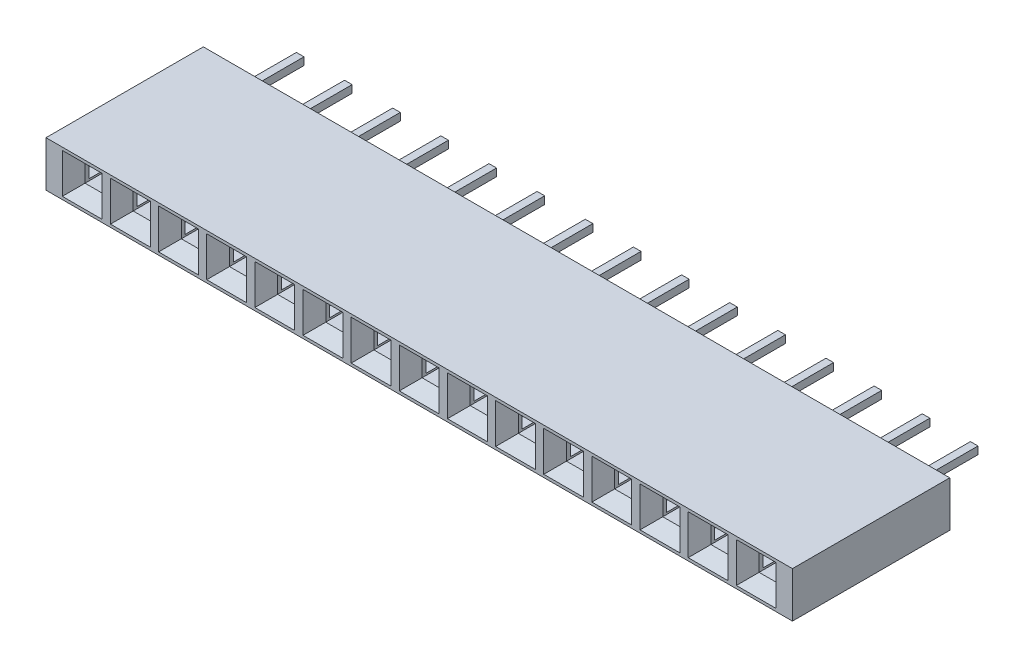
SolidWorks part; units mm, degrees
note: The reader was unsure of these and kept them because the rebuilt part matched: shared geometry of "Эскиз-БоковаяНакладка<2>".
other "Пластик"
ref_plane "Front Plane" through (0, 0, 0) normal (0, 0, 1) x (1, 0, 0)
ref_plane "Top Plane" through (0, 0, 0) normal (0, 1, 0) x (1, 0, 0)
ref_plane "Right Plane" through (0, 0, 0) normal (1, 0, 0) x (0, 0, -1)
sketch "Эскиз-ВнутреннееСечение" plane through (0, 0, 0) normal (0, 0, 1) x (1, 0, 0)
  line L0 (-1, 0.35) -> (-0.45, 0.35)
  line L1 (-1.27, -1.2) -> (1.27, -1.2)
  line L2 (-1.27, -1.2) -> (-1.27, 1.2)
  line L3 (-1.27, 1.2) -> (1.27, 1.2)
  line L4 (1.27, -1.2) -> (1.27, 1.2)
  line L5 (-1.27, -1.2) -> (1.27, 1.2) construction
  line L6 (-1.27, 1.2) -> (1.27, -1.2) construction
  line L8 (-1, -0.35) -> (-1, 0.35)
  line L9 (-0.45, 0.45) -> (0.45, 0.45)
  line L11 (0, 1.2) -> (0, -1.2) construction
  line L12 (0.45, 0.35) -> (0.45, 0.45)
  line L13 (-1.27, 0) -> (1.27, 0) construction
  line L14 (1, 0.35) -> (0.45, 0.35)
  line L15 (-0.45, 0.35) -> (-0.45, 0.45)
  line L16 (1, -0.35) -> (0.45, -0.35)
  line L17 (0.45, -0.35) -> (0.45, -0.45)
  line L18 (-0.45, -0.35) -> (-0.45, -0.45)
  line L19 (-1, -0.35) -> (-0.45, -0.35)
  line L20 (-0.45, -0.45) -> (0.45, -0.45)
  line L21 (1, -0.35) -> (1, 0.35)
  point P0 (0, 0)
  point P5 (0, 0)
  dimension "D1" = 2.4
  dimension "D2" = 2.54
  dimension "D3" = 1
  dimension "D4" = 0.35
  dimension "D5" = 0.1
  dimension "D7" = 0.55
extrude "Бобышка-ОтЦентраВверхВниз" add sketch "Эскиз-ВнутреннееСечение" against normal blind 0.4 and the other way blind 6.7 contours L8 L0 L15 L9 L12 L14 L21 L16 L17 L20 L18 L19
sketch "Эскиз-СамыйНиз" plane through (0, 0, -0.4) normal (0, 0, -1) x (-1, 0, 0)
  line L1 (1.27, 1.2) -> (1.27, -1.2) construction
  line L2 (-1.27, -1.2) -> (-1.27, 1.2) construction
  line L3 (0.45, -0.45) -> (-0.45, -0.45) construction
  line L4 (1.27, -1.2) -> (-1.27, -1.2)
  line L5 (1.27, -1.2) -> (1.27, -0.45)
  line L6 (1.27, -0.45) -> (-1.27, -0.45)
  line L7 (-1.27, -1.2) -> (-1.27, -0.45)
  line L9 (-1.27, 1.2) -> (1.27, 1.2)
  line L10 (-1.27, 1.2) -> (-1.27, 0.45)
  line L11 (-1.27, 0.45) -> (1.27, 0.45)
  line L12 (1.27, 1.2) -> (1.27, 0.45)
  line L13 (-0.45, 0.45) -> (0.45, 0.45) construction
extrude "Бобышка-СамыйНиз" add sketch "Эскиз-СамыйНиз" along normal blind 0.4
sketch "Эскиз-ВерхняяПеремычка" plane through (0, 0, 6.7) normal (0, 0, 1) x (1, 0, 0)
  line L1 (-1.27, 1.2) -> (1.27, 1.2)
  line L2 (-1.27, 1.2) -> (-1.27, -1.2)
  line L3 (-1.27, -1.2) -> (1.27, -1.2)
  line L4 (1.27, 1.2) -> (1.27, -1.2)
  line L5 (-0.45, -0.45) -> (0.45, -0.45)
  line L6 (-0.45, -0.45) -> (-0.45, 0.45)
  line L7 (-0.45, 0.45) -> (0.45, 0.45)
  line L8 (0.45, -0.45) -> (0.45, 0.45)
  line L9 (-0.45, -0.45) -> (0.45, 0.45) construction
  line L10 (-0.45, 0.45) -> (0.45, -0.45) construction
  point P4 (0, 0)
extrude "Бобышка-СамыйВерх" add sketch "Эскиз-ВерхняяПеремычка" along normal blind 0.8
chamfer "Фаска-СверхуВнутрь" distance 0.6 angle 45 4 edges at (0, -0.45, 7.5) (0.45, 0, 7.5) (0, 0.45, 7.5) (-0.45, 0, 7.5)
pattern_linear "Пластик_Массив" count 15 spacing 2.54 along (-1, 0, 0) of bodies 103
combine bodies "Соединить_Массив" operation type add bodies to combine 103 117 116 115 114 113 112 111 110 109 108 107 106 105 104
sketch "Эскиз-БоковаяНакладка" plane through (1.27, 0, 0) normal (1, 0, 0) x (0, 0, -1)
  line L1 (0.8, 1.2) -> (0.8, 0.45)
  line L2 (0.8, 0.45) -> (0.4, 0.45)
  line L3 (0.4, 0.45) -> (0.4, -0.45)
  line L4 (0.4, -0.45) -> (0.4, 0.45) construction
  line L5 (0.4, -0.45) -> (0.8, -0.45)
  line L6 (0.8, -0.45) -> (0.8, -1.2)
  line L7 (0.8, -1.2) -> (-7.5, -1.2)
  line L8 (-7.5, -1.2) -> (-7.5, 1.2)
  line L9 (-7.5, 1.2) -> (0.8, 1.2)
extrude "Бобышка-БоковаяНакладка1" add sketch "Эскиз-БоковаяНакладка" along normal blind 0.64 from surface at 0 starting at face at (1.27, 0, 1.375)
extrude "Бобышка-БоковаяНакладка2" add sketch "Эскиз-БоковаяНакладка<2>" against normal blind 0.64 from surface
sketch "Эскиз-БоковаяНакладка<2>" plane through (1.27, 0, 0) normal (1, 0, 0) x (0, 0, -1) same geometry as "Эскиз-БоковаяНакладка"
sketch "Sketch1" plane through (0, 0, -0.8) normal (0, 0, -1) x (-1, 0, 0)
  line L0 (2.34, 0.2) -> (2.74, 0.2)
  line L1 (-0.2, -0.2) -> (0.2, -0.2)
  line L2 (-0.2, -0.2) -> (-0.2, 0.2)
  line L3 (-0.2, 0.2) -> (0.2, 0.2)
  line L4 (0.2, -0.2) -> (0.2, 0.2)
  line L5 (-0.2, -0.2) -> (0.2, 0.2) construction
  line L6 (-0.2, 0.2) -> (0.2, -0.2) construction
  line L7 (2.34, -0.2) -> (2.34, 0.2)
  line L8 (2.34, -0.2) -> (2.74, -0.2)
  line L9 (2.74, -0.2) -> (2.74, 0.2)
  line L10 (4.88, 0.2) -> (5.28, 0.2)
  line L11 (4.88, -0.2) -> (4.88, 0.2)
  line L12 (4.88, -0.2) -> (5.28, -0.2)
  line L13 (5.28, -0.2) -> (5.28, 0.2)
  line L14 (7.42, 0.2) -> (7.82, 0.2)
  line L15 (7.42, -0.2) -> (7.42, 0.2)
  line L16 (7.42, -0.2) -> (7.82, -0.2)
  line L17 (7.82, -0.2) -> (7.82, 0.2)
  line L18 (9.96, 0.2) -> (10.36, 0.2)
  line L19 (9.96, -0.2) -> (9.96, 0.2)
  line L20 (9.96, -0.2) -> (10.36, -0.2)
  line L21 (10.36, -0.2) -> (10.36, 0.2)
  line L22 (12.5, 0.2) -> (12.9, 0.2)
  line L23 (12.5, -0.2) -> (12.5, 0.2)
  line L24 (12.5, -0.2) -> (12.9, -0.2)
  line L25 (12.9, -0.2) -> (12.9, 0.2)
  line L26 (15.04, 0.2) -> (15.44, 0.2)
  line L27 (15.04, -0.2) -> (15.04, 0.2)
  line L28 (15.04, -0.2) -> (15.44, -0.2)
  line L29 (15.44, -0.2) -> (15.44, 0.2)
  line L30 (17.58, 0.2) -> (17.98, 0.2)
  line L31 (17.58, -0.2) -> (17.58, 0.2)
  line L32 (17.58, -0.2) -> (17.98, -0.2)
  line L33 (17.98, -0.2) -> (17.98, 0.2)
  line L34 (20.12, 0.2) -> (20.52, 0.2)
  line L35 (20.12, -0.2) -> (20.12, 0.2)
  line L36 (20.12, -0.2) -> (20.52, -0.2)
  line L37 (20.52, -0.2) -> (20.52, 0.2)
  line L38 (22.66, 0.2) -> (23.06, 0.2)
  line L39 (22.66, -0.2) -> (22.66, 0.2)
  line L40 (22.66, -0.2) -> (23.06, -0.2)
  line L41 (23.06, -0.2) -> (23.06, 0.2)
  line L42 (25.2, 0.2) -> (25.6, 0.2)
  line L43 (25.2, -0.2) -> (25.2, 0.2)
  line L44 (25.2, -0.2) -> (25.6, -0.2)
  line L45 (25.6, -0.2) -> (25.6, 0.2)
  line L46 (27.74, 0.2) -> (28.14, 0.2)
  line L47 (27.74, -0.2) -> (27.74, 0.2)
  line L48 (27.74, -0.2) -> (28.14, -0.2)
  line L49 (28.14, -0.2) -> (28.14, 0.2)
  line L50 (30.28, 0.2) -> (30.68, 0.2)
  line L51 (30.28, -0.2) -> (30.28, 0.2)
  line L52 (30.28, -0.2) -> (30.68, -0.2)
  line L53 (30.68, -0.2) -> (30.68, 0.2)
  line L54 (32.82, 0.2) -> (33.22, 0.2)
  line L55 (32.82, -0.2) -> (32.82, 0.2)
  line L56 (32.82, -0.2) -> (33.22, -0.2)
  line L57 (33.22, -0.2) -> (33.22, 0.2)
  line L58 (35.36, 0.2) -> (35.76, 0.2)
  line L59 (35.36, -0.2) -> (35.36, 0.2)
  line L60 (35.36, -0.2) -> (35.76, -0.2)
  line L61 (35.76, -0.2) -> (35.76, 0.2)
  point P0 (0, 0)
  dimension "D1" = 0.4
  dimension "D2" = 15
extrude "Boss-Extrude1" add sketch "Sketch1" along normal blind 3.2 separate body
sketch "Sketch2" plane through (0, 0, -0.4) normal (0, 0, -1) x (-1, 0, 0)
  line L1 (-1.91, 0.45) -> (37.47, 0.45)
  line L2 (-1.91, 0.45) -> (-1.91, -0.45)
  line L3 (-1.91, -0.45) -> (37.47, -0.45)
  line L4 (37.47, 0.45) -> (37.47, -0.45)
extrude "Boss-Extrude2" add sketch "Sketch2" along normal blind 0.4
